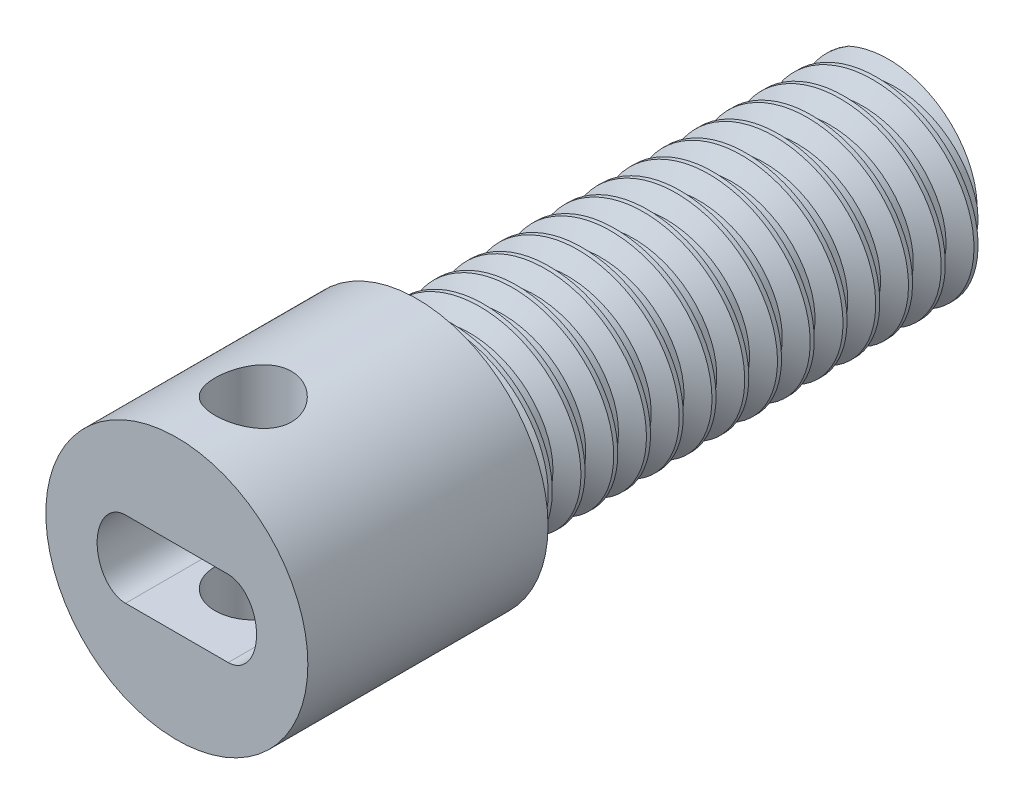
SolidWorks part; units mm, degrees
ref_plane "Front Plane" through (0, 0, 0) normal (0, 0, 1) x (1, 0, 0)
ref_plane "Top Plane" through (0, 0, 0) normal (0, 1, 0) x (1, 0, 0)
ref_plane "Right Plane" through (0, 0, 0) normal (1, 0, 0) x (0, 0, -1)
sketch "Sketch1" plane through (0, 0, 0) normal (0, 0, 1) x (1, 0, 0)
  circle A0 centre (0, 0) radius 6
  dimension "D1" = 12
extrude "Boss-Extrude1" add sketch "Sketch1" along normal blind 11
sketch "Sketch2" plane through (0, 0, 0) normal (0, 0, -1) x (-1, 0, 0)
  circle A0 centre (0, 0) radius 4.5
  dimension "D1" = 9
extrude "Boss-Extrude2" add sketch "Sketch2" along normal blind 24
thread "Thread2" pitch 1.5 method cut trim with end face yes profile "Thread Profile3" start angle 0, offset 0, length 0, pitch 1.5, diameter 9
ref_plane "Plane3" through (4.5, 0, -24) normal (0, -1, 0) x (1, 0, 0)
sketch "Thread Profile3" plane through (4.5, 0, -24) normal (0, -1, 0) x (1, 0, 0)
  line L0 (0, 0) -> (0, 1.5) construction
  line L11 (0, 0) -> (0, 1.3125)
  line L12 (0, 1.3125) -> (-0.8119, 0.8437)
  line L13 (-0.8119, 0.8437) -> (-0.8119, 0.4687)
  line L15 (-0.8119, 0.4687) -> (0, 0)
  line L17 (-0.8119, 0.6562) -> (0, 0.6562) construction
  point P2 (0, 0)
  dimension "Pitch" = 1.5
  dimension "Profile_Angle" = 60
  dimension "Profile_Land" = 0.375
  dimension "Profile_Height" = 0.8119
sketch "Sketch10" plane through (0, 0, -24) normal (0, 0, -1) x (-1, 0, 0)
  circle A0 centre (0, 0) radius 5
extrude "Cut-Extrude1" cut sketch "Sketch10" against normal blind 2
sketch "Sketch11" plane through (0, 0, 11) normal (0, 0, 1) x (1, 0, 0)
  line L0 (0, 1.75) -> (0, -1.75) construction
  line L1 (2.35, 1.75) -> (-2.35, 1.75)
  line L2 (2.35, 1.75) -> (2.35, -1.75)
  line L3 (2.35, -1.75) -> (-2.35, -1.75)
  line L4 (-2.35, 1.75) -> (-2.35, -1.75)
  line L5 (2.35, 1.75) -> (-2.35, -1.75) construction
  line L6 (2.35, -1.75) -> (-2.35, 1.75) construction
  ellipse E0 centre (-2.35, 0) end of major axis (-2.35, 1.75) minor radius 1.3
  ellipse E1 centre (2.35, 0) end of major axis (2.35, 1.75) minor radius 1.3
  point P0 (0, 0)
  dimension "D1" = 4.7
  dimension "D2" = 3.5
extrude "Cut-Extrude2" cut sketch "Sketch11" against normal blind 7 contours L4 E0 | L3 E1 L1 E0 | L4 E0 | E1 L2 | E1 L2 region at (0, 0, 11) region at (2.9017, 0, 11) region at (1.7983, 0, 11) region at (-1.7983, 0, 11) region at (-2.9017, 0, 11)
sketch "Sketch13" plane through (0, 1.75, 0) normal (0, -1, 0) x (1, 0, 0)
  line L0 (0, 11) -> (0, 4) construction
  line L1 (2.35, 11) -> (-2.35, 11) construction
  line L2 (2.35, 4) -> (-2.35, 4) construction
  circle A0 centre (0, 7.5) radius 1.75
  dimension "D1" = 3.5
extrude "Cut-Extrude4" cut sketch "Sketch13" against normal through all both and the other way through all
